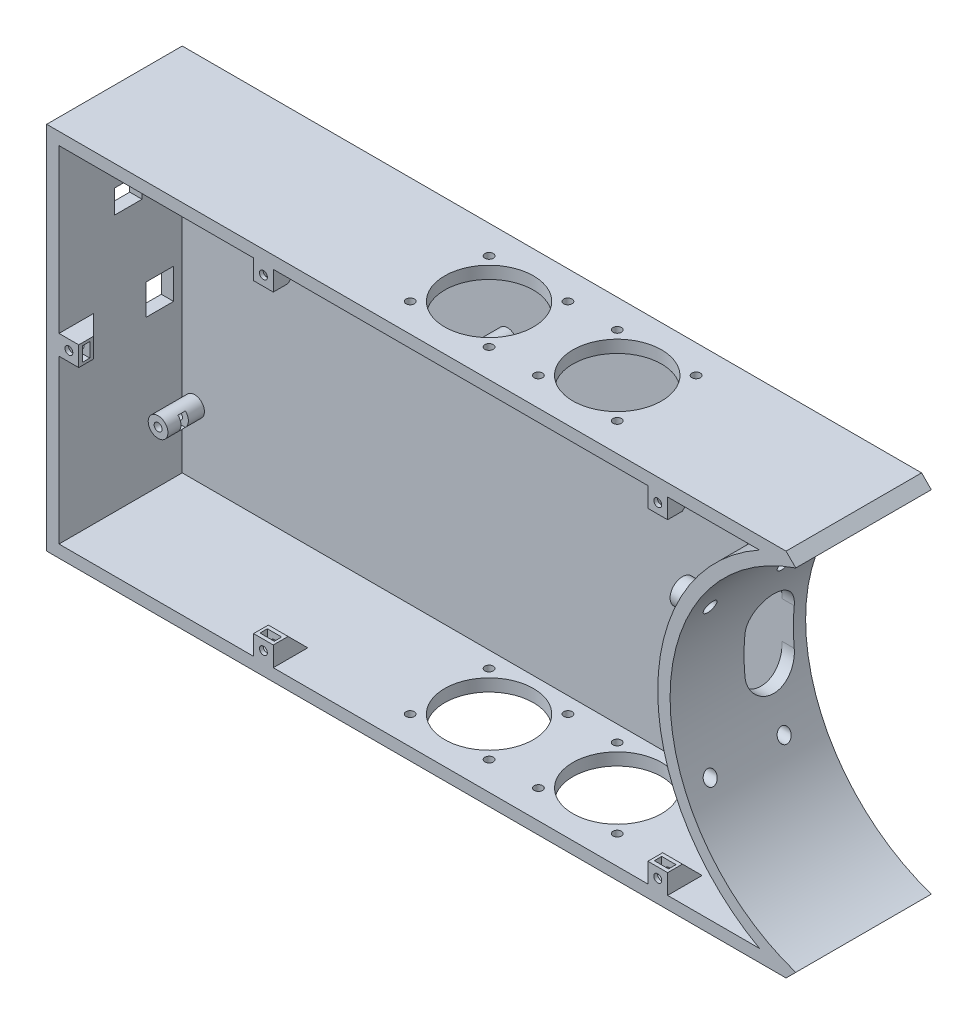
SolidWorks part; units mm, degrees
ref_plane "Alzado" through (0, 0, 0) normal (0, 0, 1) x (1, 0, 0)
ref_plane "Planta" through (0, 0, 0) normal (0, 1, 0) x (1, 0, 0)
ref_plane "Vista lateral" through (0, 0, 0) normal (1, 0, 0) x (0, 0, -1)
sketch "Croquis1" plane through (0, 0, 0) normal (0, 0, 1) x (1, 0, 0)
  line L0 (-327.9437, 75) -> (-327.9437, -75)
  line L1 (-327.9437, 75) -> (-27.9437, 75)
  line L2 (-27.9437, 75) -> (-24, 71.0563)
  line L3 (-327.9437, -75) -> (-27.9437, -75)
  line L4 (-27.9437, -75) -> (-24, -71.0563)
  circle A0 centre (0, 0) radius 75 construction
  arc A1 (-24, 71.0563) -> (-24, -71.0563) centre (0, 0) ccw
  point P6 (-327.9437, 0)
  point P11 (-75, 0)
  dimension "D1" = 150
  dimension "D2" = 150
  dimension "D3" = 300
  dimension "D4" = 135
  dimension "D5" = 24
extrude "Saliente-Extruir1" add sketch "Croquis1" along normal blind 55
sketch "Croquis2" plane through (0, 0, 55) normal (0, 0, 1) x (1, 0, 0)
  line L2 (-27.9437, 70) -> (-327.9437, 70)
  line L3 (-38.7298, 70) -> (-322.9437, 70)
  line L5 (-322.9437, 75) -> (-322.9437, -75)
  line L6 (-322.9437, 70) -> (-322.9437, -70)
  line L8 (-327.9437, -70) -> (-27.9437, -70)
  line L9 (-322.9437, -70) -> (-38.7298, -70)
  arc A2 (-25.6, 75.7934) -> (-25.6, -75.7934) centre (0, 0) ccw
  arc A3 (-38.7298, 70) -> (-38.7298, -70) centre (0, 0) ccw
  dimension "D1" = 5
  dimension "D2" = 5
  dimension "D3" = 5
  dimension "D4" = 5
extrude "Cortar-Extruir1" cut sketch "Croquis2" against normal blind 50
sketch "Croquis3" plane through (0, 0, 0) normal (1, 0, 0) x (0, 0, -1)
  line L0 (-15, 7.5) -> (-15, -7.5) construction
  line L1 (-5, 7.5) -> (-5, -7.5)
  line L2 (-25, 7.5) -> (-25, -7.5)
  line L3 (-5, 70) -> (-5, -70) construction
  arc A0 (-5, 7.5) -> (-25, 7.5) centre (-15, 7.5) ccw
  arc A1 (-25, -7.5) -> (-5, -7.5) centre (-15, -7.5) ccw
  point P2 (-15, 0)
  dimension "D2" = 10
  dimension "D1" = 15
extrude "Cortar-Extruir2" cut sketch "Croquis3" against normal blind 82
sketch "Croquis4" plane through (0, 0, 0) normal (1, 0, 0) x (0, 0, -1)
  line L0 (-15, 30) -> (-15, -30) construction
  line L1 (-15, 30) -> (-45, 30) construction
  line L2 (-45, 30) -> (-45, -30) construction
  line L3 (-15, -30) -> (-45, -30) construction
  line L4 (-15, 30) -> (-45, -30) construction
  line L5 (-45, 30) -> (-15, -30) construction
  circle A0 centre (-45, -30) radius 2.6
  circle A1 centre (-15, -30) radius 2.6
  circle A2 centre (-15, 30) radius 2.6
  circle A3 centre (-45, 30) radius 2.6
  point P0 (-30, 0)
  dimension "D3" = 5.2
  dimension "D1" = 60
  dimension "D2" = 30
  dimension "D4" = 30
extrude "Cortar-Extruir3" cut sketch "Croquis4" against normal blind 82
ref_plane "Plano1" through (-80, 0, 0) normal (-1, 0, 0) x (0, 0, 1)
sketch "Croquis5" plane through (-80, 0, 0) normal (-1, 0, 0) x (0, 0, 1)
  circle A0 centre (45, -30) radius 2.6 construction
  circle A1 centre (15, -30) radius 2.6 construction
  circle A2 centre (45, 30) radius 2.6 construction
  circle A3 centre (15, 30) radius 2.6 construction
  circle A4 centre (45, -30) radius 2.6
  circle A5 centre (15, -30) radius 2.6
  circle A6 centre (45, 30) radius 2.6
  circle A7 centre (15, 30) radius 2.6
  circle A8 centre (45, 30) radius 5
  circle A9 centre (15, 30) radius 5
  circle A10 centre (45, -30) radius 5
  circle A11 centre (15, -30) radius 5
  dimension "D1" = 10
extrude "Saliente-Extruir2" add sketch "Croquis5" against normal up to surface (5.838 mm away) up to face at (-73.907, -30.6228, 47.5243)
sketch "Croquis6" plane through (0, 0, 5) normal (0, 0, 1) x (1, 0, 0)
  line L0 (-322.9437, 70) -> (-322.9437, -70) construction
  line L1 (-97.9437, -48) -> (-322.9437, -48) construction
  line L2 (-97.9437, -48) -> (-97.9437, 48) construction
  line L3 (-97.9437, 48) -> (-322.9437, 48) construction
  line L4 (-322.9437, -48) -> (-322.9437, 48) construction
  line L5 (-97.9437, -48) -> (-322.9437, 48) construction
  line L6 (-97.9437, 48) -> (-322.9437, -48) construction
  circle A0 centre (-302.9437, 44) radius 1.6
  circle A1 centre (-317.9437, -44) radius 1.6
  circle A2 centre (-190.9437, 43) radius 1.6
  circle A3 centre (-102.9437, 43) radius 1.6
  circle A4 centre (-102.9437, -43) radius 1.6
  point P0 (-210.4437, 0)
  dimension "D3" = 3.2
  dimension "D1" = 225
  dimension "D2" = 96
  dimension "D4" = 4
  dimension "D5" = 20
  dimension "D6" = 93
  dimension "D7" = 5
  dimension "D8" = 5
  dimension "D9" = 5
  dimension "D10" = 5
  dimension "D11" = 5
  dimension "D12" = 4
  dimension "D13" = 5
extrude "Cortar-Extruir4" cut sketch "Croquis6" against normal blind 82
sketch "Croquis7" plane through (-327.9437, 0, 0) normal (-1, 0, 0) x (0, 0, 1)
  line L0 (55, 75) -> (55, -75) construction
  line L1 (21.3, 43.8) -> (32.5, 43.8)
  line L2 (21.3, 43.8) -> (21.3, 34.3)
  line L3 (21.3, 34.3) -> (32.5, 34.3)
  line L4 (32.5, 43.8) -> (32.5, 34.3)
  line L5 (21.3, 43.8) -> (32.5, 34.3) construction
  line L6 (21.3, 34.3) -> (32.5, 43.8) construction
  line L7 (55, 75) -> (0, 75) construction
  point P0 (26.9, 39.05)
  dimension "D1" = 22.5
  dimension "D2" = 31.2
  dimension "D3" = 11.2
  dimension "D4" = 9.5
extrude "Cortar-Extruir5" cut sketch "Croquis7" against normal blind 13
sketch "Croquis8" plane through (-327.9437, 0, 0) normal (-1, 0, 0) x (0, 0, 1)
  line L0 (0, 75) -> (0, -75) construction
  line L1 (19.7, -8) -> (8.5, -8)
  line L2 (19.7, -8) -> (19.7, 4.4)
  line L3 (19.7, 4.4) -> (8.5, 4.4)
  line L4 (8.5, -8) -> (8.5, 4.4)
  line L5 (19.7, -8) -> (8.5, 4.4) construction
  line L6 (19.7, 4.4) -> (8.5, -8) construction
  line L7 (55, -75) -> (0, -75) construction
  point P0 (14.1, -1.8)
  point P9 (14.1, -8)
  dimension "D1" = 8.5
  dimension "D2" = 67
  dimension "D3" = 11.2
  dimension "D4" = 12.4
extrude "Cortar-Extruir6" cut sketch "Croquis8" against normal blind 13
sketch "Croquis9" plane through (0, 0, 5) normal (0, 0, 1) x (1, 0, 0)
  circle A0 centre (-302.9437, 44) radius 4
  circle A1 centre (-317.9437, -44) radius 4
  circle A2 centre (-190.9437, 43) radius 4
  circle A3 centre (-102.9437, 43) radius 4
  circle A4 centre (-102.9437, -43) radius 4
  circle A5 centre (-190.9437, 43) radius 1.6 construction
  circle A6 centre (-317.9437, -44) radius 1.6 construction
  circle A7 centre (-102.9437, 43) radius 1.6 construction
  circle A8 centre (-102.9437, -43) radius 1.6 construction
  circle A9 centre (-102.9437, -43) radius 1.6
  circle A10 centre (-102.9437, 43) radius 1.6
  circle A11 centre (-317.9437, -44) radius 1.6
  circle A12 centre (-190.9437, 43) radius 1.6
  circle A13 centre (-302.9437, 44) radius 1.6 construction
  circle A14 centre (-302.9437, 44) radius 1.6
  dimension "D1" = 8
extrude "Saliente-Extruir3" add sketch "Croquis9" along normal blind 14.8
sketch "Croquis10" plane through (0, -75, 0) normal (0, -1, 0) x (1, 0, 0)
  line L0 (-159.9437, 11.5) -> (-191.9437, 11.5) construction
  line L1 (-159.9437, 11.5) -> (-159.9437, 43.5) construction
  line L2 (-159.9437, 43.5) -> (-191.9437, 43.5) construction
  line L3 (-191.9437, 11.5) -> (-191.9437, 43.5) construction
  line L4 (-159.9437, 11.5) -> (-191.9437, 43.5) construction
  line L5 (-159.9437, 43.5) -> (-191.9437, 11.5) construction
  line L6 (-107.9437, 11.5) -> (-139.9437, 11.5) construction
  line L7 (-107.9437, 11.5) -> (-107.9437, 43.5) construction
  line L8 (-107.9437, 43.5) -> (-139.9437, 43.5) construction
  line L9 (-139.9437, 11.5) -> (-139.9437, 43.5) construction
  line L10 (-107.9437, 11.5) -> (-139.9437, 43.5) construction
  line L11 (-107.9437, 43.5) -> (-139.9437, 11.5) construction
  line L12 (-327.9437, 55) -> (-327.9437, 0) construction
  line L13 (-27.9437, 55) -> (-27.9437, 0) construction
  circle A0 centre (-191.9437, 43.5) radius 1.7
  circle A1 centre (-159.9437, 43.5) radius 1.7
  circle A2 centre (-191.9437, 11.5) radius 1.7
  circle A3 centre (-159.9437, 11.5) radius 1.7
  circle A4 centre (-139.9437, 43.5) radius 1.7
  circle A5 centre (-107.9437, 43.5) radius 1.7
  circle A6 centre (-139.9437, 11.5) radius 1.7
  circle A7 centre (-107.9437, 11.5) radius 1.7
  circle A12 centre (-175.9437, 27.5) radius 18
  circle A13 centre (-123.9437, 27.5) radius 18
  point P4 (-175.9437, 27.5)
  point P13 (-123.9437, 27.5)
  point P20 (-327.9437, 27.5)
  dimension "D3" = 3.4
  dimension "D6" = 3.4
  dimension "D9" = 36
  dimension "D1" = 32
  dimension "D2" = 32
  dimension "D4" = 32
  dimension "D5" = 32
  dimension "D7" = 20
  dimension "D8" = 80
extrude "Cortar-Extruir7" cut sketch "Croquis10" against normal blind 14.8
mirror "Simetría1" about plane through (0, 0, 0) normal (0, 1, 0) of "Cortar-Extruir7"
ref_plane "Plano2" through (0, 0, 13) normal (0, 0, 1) x (1, 0, 0)
sketch "Croquis11" plane through (0, 0, 13) normal (0, 0, 1) x (1, 0, 0)
  line L0 (-301.2687, 46.9012) -> (-296.5962, 46.9012)
  line L1 (-299.5937, 44) -> (-301.2687, 46.9012) construction
  line L2 (-301.2687, 46.9012) -> (-304.6187, 46.9012)
  line L3 (-304.6187, 46.9012) -> (-306.2937, 44)
  line L4 (-306.2937, 44) -> (-304.6187, 41.0988)
  line L5 (-304.6187, 41.0988) -> (-301.2687, 41.0988)
  line L6 (-301.2687, 41.0988) -> (-299.5937, 44) construction
  line L7 (-314.5937, -44) -> (-316.2687, -41.0988) construction
  line L8 (-316.2687, -41.0988) -> (-319.6187, -41.0988)
  line L9 (-319.6187, -41.0988) -> (-321.2937, -44)
  line L10 (-321.2937, -44) -> (-319.6187, -46.9012)
  line L11 (-319.6187, -46.9012) -> (-316.2687, -46.9012)
  line L12 (-316.2687, -46.9012) -> (-314.5937, -44) construction
  line L13 (-187.5937, 43) -> (-189.2687, 45.9012)
  line L14 (-189.2687, 45.9012) -> (-192.6187, 45.9012)
  line L15 (-192.6187, 45.9012) -> (-194.2937, 43) construction
  line L16 (-194.2937, 43) -> (-192.6187, 40.0988) construction
  line L17 (-192.6187, 40.0988) -> (-189.2687, 40.0988)
  line L18 (-189.2687, 40.0988) -> (-187.5937, 43)
  line L19 (-99.5937, 43) -> (-101.2687, 45.9012)
  line L20 (-101.2687, 45.9012) -> (-104.6187, 45.9012)
  line L21 (-104.6187, 45.9012) -> (-106.2937, 43) construction
  line L22 (-106.2937, 43) -> (-104.6187, 40.0988) construction
  line L23 (-104.6187, 40.0988) -> (-101.2687, 40.0988)
  line L24 (-101.2687, 40.0988) -> (-99.5937, 43)
  line L25 (-99.5937, -43) -> (-101.2687, -40.0988)
  line L26 (-101.2687, -40.0988) -> (-104.6187, -40.0988)
  line L27 (-104.6187, -40.0988) -> (-106.2937, -43) construction
  line L28 (-106.2937, -43) -> (-104.6187, -45.9012) construction
  line L29 (-104.6187, -45.9012) -> (-101.2687, -45.9012)
  line L30 (-101.2687, -45.9012) -> (-99.5937, -43)
  line L31 (-296.5962, 46.9012) -> (-296.5962, 41.0988)
  line L32 (-296.5962, 41.0988) -> (-301.2687, 41.0988)
  line L33 (-192.6187, 45.9012) -> (-196.6834, 45.9012)
  line L34 (-196.6834, 45.9012) -> (-196.6834, 40.0988)
  line L35 (-196.6834, 40.0988) -> (-192.6187, 40.0988)
  line L36 (-104.6187, 45.9012) -> (-110.7706, 45.9012)
  line L37 (-110.7706, 45.9012) -> (-110.7706, 40.0988)
  line L38 (-110.7706, 40.0988) -> (-104.6187, 40.0988)
  line L39 (-104.6187, -40.0988) -> (-109.0472, -40.0988)
  line L40 (-109.0472, -40.0988) -> (-109.1678, -45.9012)
  line L41 (-109.1678, -45.9012) -> (-104.6187, -45.9012)
  line L42 (-316.2687, -46.9012) -> (-310.7216, -46.9012)
  line L43 (-310.7216, -46.9012) -> (-310.7216, -41.0988)
  line L44 (-310.7216, -41.0988) -> (-316.2687, -41.0988)
  line L45 (-38.7298, 70) -> (-322.9437, 70) construction
  line L46 (-322.9437, -70) -> (-38.7298, -70) construction
  circle A0 centre (-302.9437, 44) radius 3.35 construction
  circle A1 centre (-317.9437, -44) radius 3.35 construction
  circle A2 centre (-190.9437, 43) radius 3.35 construction
  circle A3 centre (-102.9437, 43) radius 3.35 construction
  circle A4 centre (-102.9437, -43) radius 3.35 construction
  dimension "D1" = 6.7
extrude "Cortar-Extruir8" cut sketch "Croquis11" against normal blind 1.5 and the other way blind 1.5
sketch "Croquis12" plane through (0, 0, 0) normal (0, 1, 0) x (1, 0, 0)
  line L0 (-322.9437, -41) -> (-322.9437, -55)
  line L1 (-322.9437, -55) -> (-314.9437, -55)
  line L6 (-27.9437, -55) -> (-327.9437, -55) construction
  line L7 (-322.9437, -19.7) -> (-322.9437, -8.5) construction
  line L8 (-314.9437, -55) -> (-314.9437, -49)
  line L9 (-314.9437, -49) -> (-322.9437, -41)
  dimension "D1" = 8
  dimension "D2" = 45
  dimension "D3" = 6
extrude "Saliente-Extruir4" add sketch "Croquis12" along normal blind 4 and the other way blind 4
sketch "Croquis14" plane through (-80, 0, 0) normal (-1, 0, 0) x (0, 0, 1)
  line L0 (55, 70) -> (55, 62)
  line L1 (55, -70) -> (55, 70) construction
  line L3 (5, 70) -> (55, 70) construction
  line L4 (41, 70) -> (55, 70)
  line L5 (55, -70) -> (55, -62)
  line L7 (5, -70) -> (55, -70) construction
  line L8 (41, -70) -> (55, -70)
  line L9 (55, 62) -> (49, 62)
  line L10 (49, 62) -> (41, 70)
  line L11 (41, -70) -> (49, -62)
  line L12 (49, -62) -> (55, -62)
  dimension "D2" = 8
  dimension "D3" = 45
  dimension "D4" = 8
  dimension "D5" = 6
extrude "Saliente-Extruir5" add sketch "Croquis14" along normal blind 4 and the other way blind 4
sketch "Croquis13" plane through (0, 0, 55) normal (0, 0, 1) x (1, 0, 0)
  line L0 (-322.9437, 4) -> (-314.9437, -4) construction
  line L1 (-314.9437, 4) -> (-322.9437, -4) construction
  line L2 (-84, 70) -> (-76, 62) construction
  line L4 (-76, 70) -> (-84, 62) construction
  line L6 (-84, -62) -> (-76, -70) construction
  line L7 (-84, -70) -> (-76, -62) construction
  line L8 (-76, -70) -> (-76, -62) construction
  line L9 (-84, -70) -> (-84, -62) construction
  circle A0 centre (-318.9437, 0) radius 1.6
  circle A2 centre (-80, -66) radius 1.6
  circle A3 centre (-80, 66) radius 1.6
  dimension "D1" = 3.2
extrude "Cortar-Extruir9" cut sketch "Croquis13" against normal blind 14
ref_plane "Plano3" through (-160, 0, 0) normal (-1, 0, 0) x (0, 0, 1)
ref_plane "Plano4" through (0, 0, 52) normal (0, 0, 1) x (1, 0, 0)
mirror "Simetría2" about plane through (-160, 0, 0) normal (-1, 0, 0) of "Cortar-Extruir9", "Saliente-Extruir5"
sketch "Croquis17" plane through (0, 0, 52) normal (0, 0, 1) x (1, 0, 0)
  line L0 (-322.9437, 70) -> (-322.9437, 4) construction
  line L1 (-315.5937, 0) -> (-317.2687, 2.9012) construction
  line L2 (-317.2687, 2.9012) -> (-320.6187, 2.9012)
  line L3 (-320.6187, 2.9012) -> (-322.2937, 0)
  line L4 (-322.2937, 0) -> (-320.6187, -2.9012)
  line L5 (-320.6187, -2.9012) -> (-317.2687, -2.9012)
  line L6 (-317.2687, -2.9012) -> (-315.5937, 0) construction
  line L7 (-240, -62.65) -> (-242.9012, -64.325) construction
  line L8 (-242.9012, -64.325) -> (-242.9012, -67.675)
  line L9 (-242.9012, -67.675) -> (-240, -69.35)
  line L10 (-240, -69.35) -> (-237.0988, -67.675)
  line L11 (-237.0988, -67.675) -> (-237.0988, -64.325)
  line L12 (-237.0988, -64.325) -> (-240, -62.65) construction
  line L13 (-80, -62.65) -> (-82.9012, -64.325) construction
  line L14 (-82.9012, -64.325) -> (-82.9012, -67.675)
  line L15 (-82.9012, -67.675) -> (-80, -69.35)
  line L16 (-80, -69.35) -> (-77.0988, -67.675)
  line L17 (-77.0988, -67.675) -> (-77.0988, -64.325)
  line L18 (-77.0988, -64.325) -> (-80, -62.65) construction
  line L19 (-80, 62.65) -> (-77.0988, 64.325) construction
  line L20 (-77.0988, 64.325) -> (-77.0988, 67.675)
  line L21 (-77.0988, 67.675) -> (-80, 69.35)
  line L22 (-80, 69.35) -> (-82.9012, 67.675)
  line L23 (-82.9012, 67.675) -> (-82.9012, 64.325)
  line L24 (-82.9012, 64.325) -> (-80, 62.65) construction
  line L25 (-240, 62.65) -> (-237.0988, 64.325) construction
  line L26 (-237.0988, 64.325) -> (-237.0988, 67.675)
  line L27 (-237.0988, 67.675) -> (-240, 69.35)
  line L28 (-240, 69.35) -> (-242.9012, 67.675)
  line L29 (-242.9012, 67.675) -> (-242.9012, 64.325)
  line L30 (-242.9012, 64.325) -> (-240, 62.65) construction
  line L31 (-322.9437, -70) -> (-244, -70) construction
  line L32 (-317.2687, 2.9012) -> (-310.6187, 2.9012)
  line L33 (-310.6187, 2.9012) -> (-310.6187, -2.9012)
  line L34 (-310.6187, -2.9012) -> (-317.2687, -2.9012)
  line L35 (-242.9012, 64.325) -> (-242.9012, 57.675)
  line L36 (-242.9012, 57.675) -> (-237.0988, 57.675)
  line L37 (-237.0988, 57.675) -> (-237.0988, 64.325)
  line L38 (-82.9012, 64.325) -> (-82.9012, 57.675)
  line L39 (-82.9012, 57.675) -> (-76.8873, 57.675)
  line L40 (-76.8873, 57.675) -> (-77.0988, 64.325)
  line L41 (-82.9012, -64.325) -> (-82.9012, -57.675)
  line L42 (-82.9012, -57.675) -> (-77.0988, -57.675)
  line L43 (-77.0988, -57.675) -> (-77.0988, -64.325)
  line L44 (-242.9012, -64.325) -> (-242.9012, -57.675)
  line L45 (-242.9012, -57.675) -> (-237.0988, -57.675)
  line L46 (-237.0988, -57.675) -> (-237.0988, -64.325)
  circle A0 centre (-318.9437, 0) radius 3.35 construction
  circle A1 centre (-240, -66) radius 3.35 construction
  circle A2 centre (-80, -66) radius 3.35 construction
  circle A3 centre (-80, 66) radius 3.35 construction
  circle A4 centre (-240, 66) radius 3.35 construction
  dimension "D1" = 6.7
  dimension "D2" = 10
extrude "Cortar-Extruir10" cut sketch "Croquis17" against normal blind 1.5 and the other way blind 1.5
